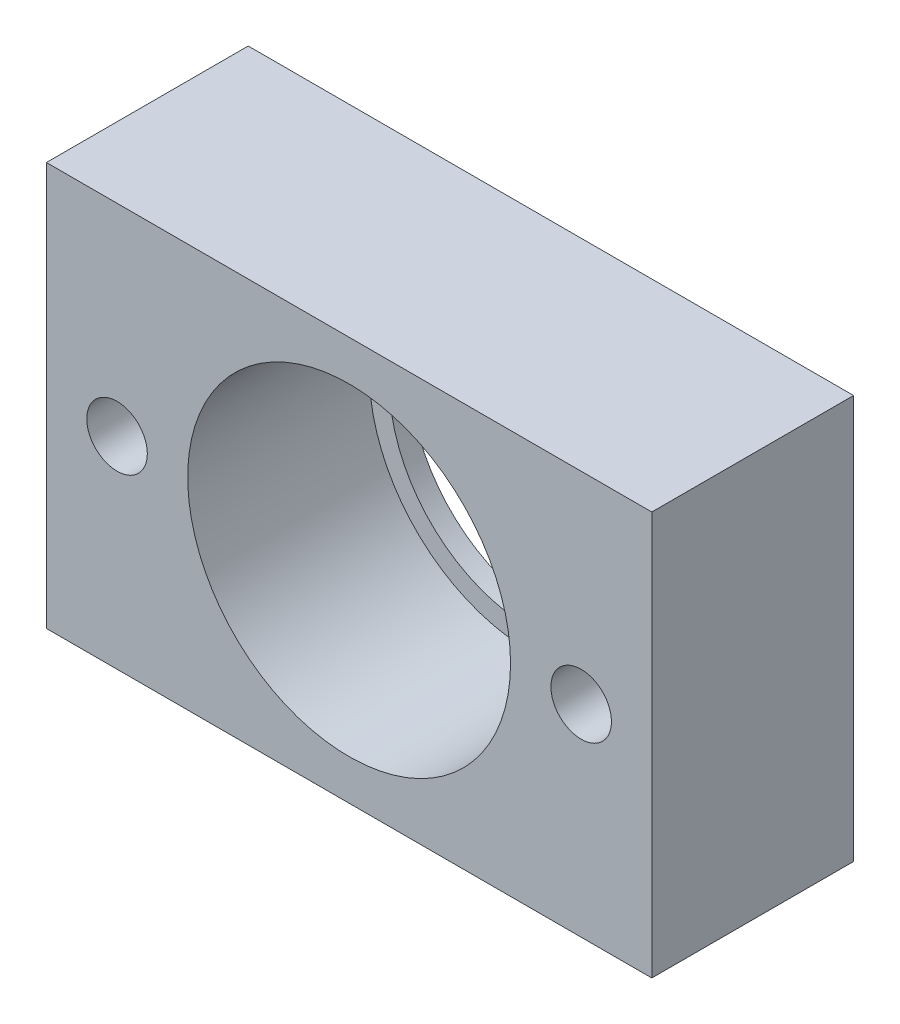
SolidWorks part; units mm, degrees
ref_plane "Front Plane" through (0, 0, 0) normal (0, 0, 1) x (1, 0, 0)
ref_plane "Top Plane" through (0, 0, 0) normal (0, 1, 0) x (1, 0, 0)
ref_plane "Right Plane" through (0, 0, 0) normal (1, 0, 0) x (0, 0, -1)
sketch "Sketch1" plane through (0, 0, 0) normal (0, 0, 1) x (1, 0, 0)
  line L1 (-7.7401, 17.8814) -> (22.2599, 17.8814)
  line L2 (-7.7401, 17.8814) -> (-7.7401, -2.1186)
  line L3 (-7.7401, -2.1186) -> (22.2599, -2.1186)
  line L4 (22.2599, 17.8814) -> (22.2599, -2.1186)
  circle A0 centre (7.2599, 7.8814) radius 8
  circle A1 centre (7.2599, 7.8814) radius 7
  circle A2 centre (-4.2401, 7.8814) radius 1.5
  circle A3 centre (18.7599, 7.8814) radius 1.5
  dimension "D3" = 16
  dimension "D4" = 15
  dimension "D5" = 10
  dimension "D6" = 1
  dimension "D7" = 3.5
  dimension "D8" = 3
  dimension "D9" = 3
  dimension "D10" = 3.5
  dimension "D1" = 20
  dimension "D2" = 30
extrude "Boss-Extrude1" add sketch "Sketch1" along normal blind 10 contours L4 L1 L2 L3 A3 A2 A0 region at (7.2599, 17.5208, 0)
extrude "Boss-Extrude2" add sketch "Sketch1<3>" along normal blind 1 contours A0 A1 region at (-0.5138, 7.8814, 0)
sketch "Sketch1<3>" plane through (0, 0, 0) normal (0, 0, 1) x (1, 0, 0) same geometry as "Sketch1"
